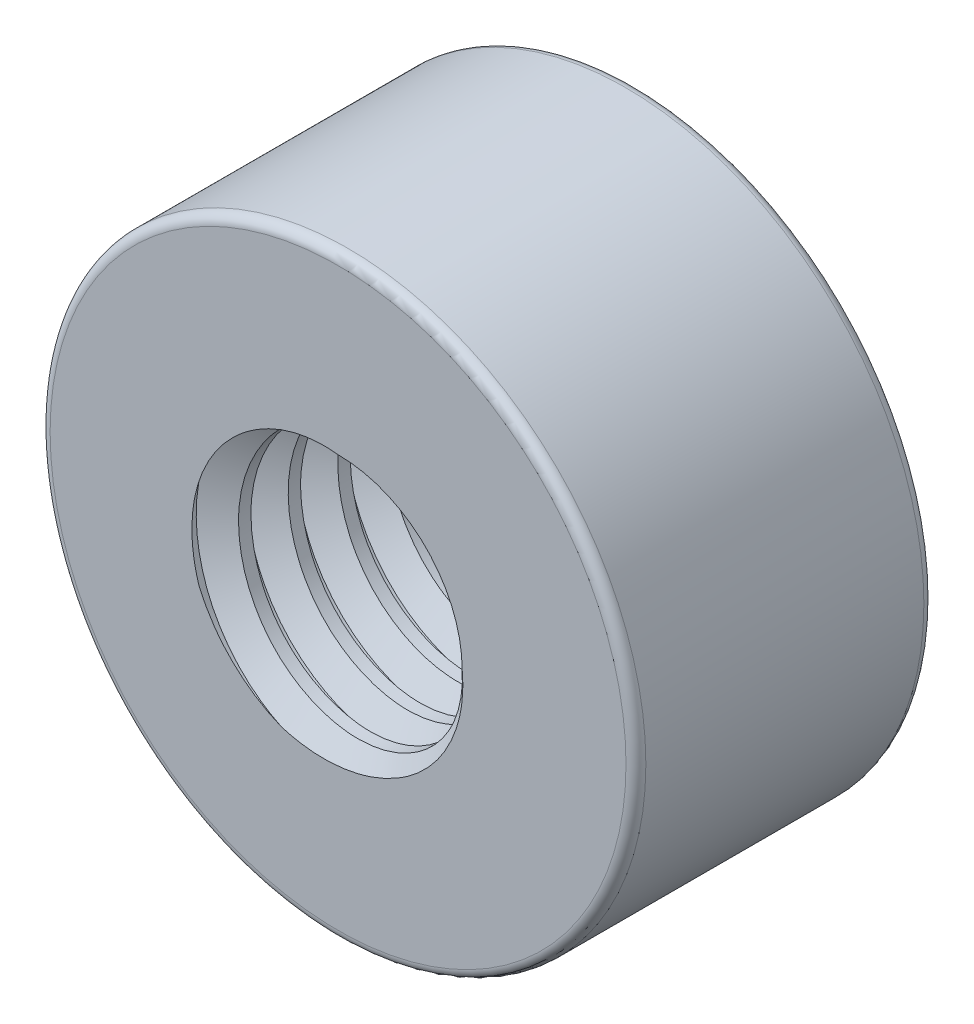
SolidWorks part; units mm, degrees
ref_plane "前视基准面" through (0, 0, 0) normal (0, 0, 1) x (1, 0, 0)
ref_plane "上视基准面" through (0, 0, 0) normal (0, 1, 0) x (1, 0, 0)
ref_plane "右视基准面" through (0, 0, 0) normal (1, 0, 0) x (0, 0, -1)
sketch "草图3" plane through (0, 0, 0) normal (0, 0, 1) x (1, 0, 0)
  circle A0 centre (0, 0) radius 3
  dimension "D1" = 6
extrude "凸台-拉伸1" add sketch "草图3" along normal blind 3
fillet "圆角1" radius 0.1 2 edges at (3, 0, 0) (3, 0, 3)
sketch "草图5" plane through (0, 0, 3) normal (0, 0, 1) x (1, 0, 0)
  circle A0 centre (0, 0) radius 1.25
  dimension "D1" = 2.5
extrude "切除-拉伸1" cut sketch "草图5" against normal blind 3
thread "螺纹线2" pitch 0.5 method cut profile "螺纹线轮廓3" start angle 0, offset 1, length 0, pitch 0.5, diameter 2.5
ref_plane "基准面3" through (1.25, 0, -1) normal (0, -1, 0) x (1, 0, 0)
sketch "螺纹线轮廓3" plane through (1.25, 0, -1) normal (0, -1, 0) x (1, 0, 0)
  line L0 (0, 0) -> (0, 0.5) construction
  line L1 (0, 0) -> (0.2706, 0.1562)
  line L2 (0.2706, 0.1562) -> (0.2706, 0.2187)
  line L3 (0.2706, 0.2187) -> (0, 0.375)
  line L4 (0.2706, 0.1875) -> (0, 0.1875) construction
  line L11 (0, 0) -> (0, 0.375)
  point P2 (0, 0)
  dimension "Pitch" = 0.5
  dimension "Profile_Angle" = 60
  dimension "Profile_Land" = 0.0625
  dimension "Profile_Height" = 0.2706
